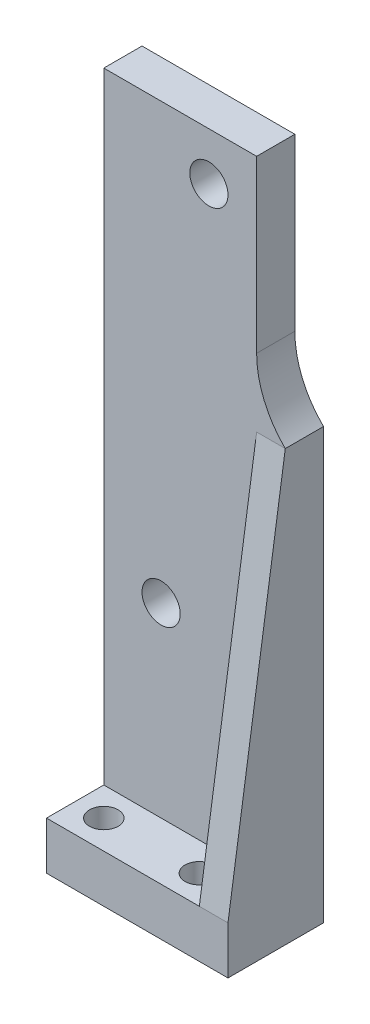
SolidWorks part; units mm, degrees
ref_plane "前视基准面" through (0, 0, 0) normal (0, 0, 1) x (1, 0, 0)
ref_plane "上视基准面" through (0, 0, 0) normal (0, 1, 0) x (1, 0, 0)
ref_plane "右视基准面" through (0, 0, 0) normal (1, 0, 0) x (0, 0, -1)
sketch "草图1" plane through (0, 0, 0) normal (0, 1, 0) x (1, 0, 0)
  line L0 (-6, 0) -> (-3, 0)
  line L1 (-6, 3) -> (10, 3)
  line L2 (-6, 3) -> (-6, -3)
  line L3 (-6, -3) -> (10, -3)
  line L4 (10, 3) -> (10, -3)
  line L5 (-6, 3) -> (10, -3) construction
  line L6 (-6, -3) -> (10, 3) construction
  line L7 (10, 0) -> (7, 0)
  circle A5 centre (-3, 0) radius 1.5
  circle A6 centre (7, 0) radius 1.5
extrude "凸台-拉伸1" add sketch "草图1" along normal blind 5 contours L7 L4 L1 L2 L0 | L0 L2 L3 L4 L7 region at (2, 0, 0)
sketch "草图2" plane through (0, 0, -3) normal (0, 0, -1) x (-1, 0, 0)
  line L0 (-10, 0) -> (-10, 70)
  line L1 (-10, 70) -> (6, 70)
  line L2 (6, 70) -> (6, 0)
  line L3 (6, 0) -> (-10, 0)
extrude "凸台-拉伸2" add sketch "草图2" along normal blind 4 contours L0 L1 L2 L3
sketch "草图3" plane through (0, 0, -7) normal (0, 0, -1) x (-1, 0, 0)
  circle A0 centre (-5, 65) radius 2
extrude "切除-拉伸1" cut sketch "草图3" against normal through all contours A0
sketch "草图4" plane through (0, 0, -7) normal (0, 0, -1) x (-1, 0, 0)
  line L0 (0, 0) -> (0, 24.5)
  circle A0 centre (0, 24.5) radius 2
extrude "切除-拉伸2" cut sketch "草图4" against normal through all contours A0
sketch "草图5" plane through (0, 0, -7) normal (0, 0, -1) x (-1, 0, 0)
  circle A0 centre (-5, 65) radius 3.5
extrude "切除-拉伸3" cut sketch "草图5" against normal blind 0.8
sketch "草图6" plane through (10, 0, 0) normal (1, 0, 0) x (0, 0, -1)
  line L0 (-3, 5) -> (3, 5)
  line L1 (3, 5) -> (3, 45)
  line L3 (3, 45) -> (-3, 5)
  line L4 (-3, 5) -> (-3, 0)
  line L5 (-3, 0) -> (7, 0)
  line L6 (7, 0) -> (7, 45)
  line L7 (7, 0) -> (7, 70) construction
  line L8 (7, 45) -> (3, 45)
  line M2 (-3, 0) -> (7, 0)
  line M3 (7, 0) -> (7, 70)
  line M5 (3, 70) -> (3, 5)
  line M6 (3, 5) -> (-3, 5)
  line M7 (-3, 5) -> (-3, 0)
extrude "凸台-拉伸3" add sketch "草图6" along normal blind 3 contours L8 M3 M5 M6 M7 M2 | L3 M5 M6 region at (10, 18.3333, -1) region at (10, 19.6429, -4.2857)
fillet "圆角1" radius 10 1 edges at (10, 45, -5)
